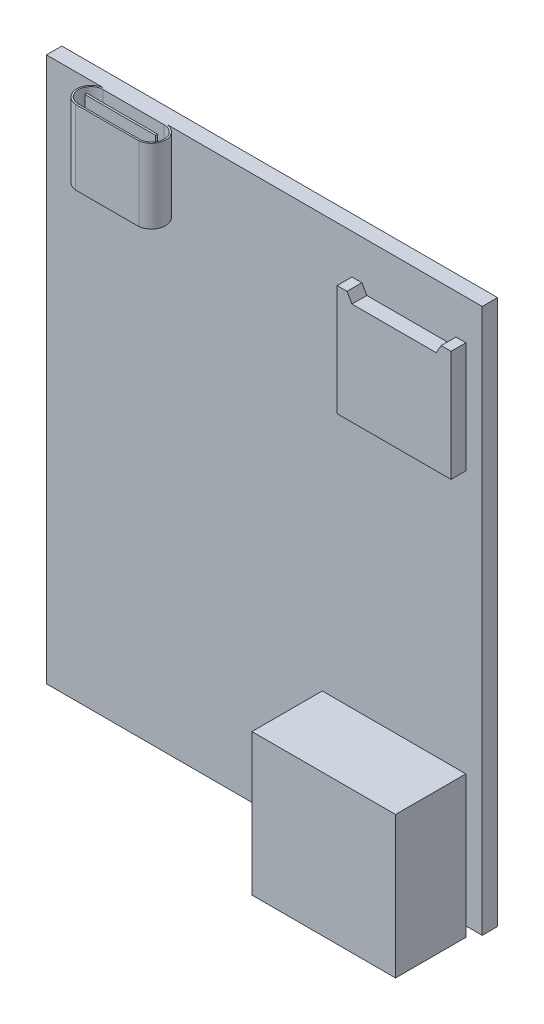
SolidWorks part; units mm, degrees
ref_plane "Front Plane" through (0, 0, 0) normal (1, 0, 0) x (0, 1, 0)
ref_plane "Top Plane" through (0, 0, 0) normal (0, 0, 1) x (0, 1, 0)
ref_plane "Right Plane" through (0, 0, 0) normal (0, 1, 0) x (-1, 0, 0)
sketch "Sketch1" plane through (0, 0, 0) normal (0, 0, 1) x (0, 1, 0)
  line L1 (-27.5, -22) -> (27.5, -22)
  line L2 (-27.5, -22) -> (-27.5, 22)
  line L3 (-27.5, 22) -> (27.5, 22)
  line L4 (27.5, -22) -> (27.5, 22)
  line L5 (-27.5, -22) -> (27.5, 22) construction
  line L6 (-27.5, 22) -> (27.5, -22) construction
  point P0 (0, 0)
  dimension "D1" = 55
  dimension "D2" = 44
extrude "Boss-Extrude1" add sketch "Sketch1" along normal blind 1.55
sketch "Sketch2" plane through (0, 0, 1.55) normal (0, 0, 1) x (1, 0, 0)
  line L0 (22, -27.5) -> (22, 27.5) construction
  line L1 (5.85, -14.2) -> (20.35, -14.2)
  line L2 (5.85, -14.2) -> (5.85, -28.5)
  line L3 (5.85, -28.5) -> (20.35, -28.5)
  line L4 (20.35, -14.2) -> (20.35, -28.5)
  line L5 (5.85, -14.2) -> (20.35, -28.5) construction
  line L6 (5.85, -28.5) -> (20.35, -14.2) construction
  line L7 (-22, -27.5) -> (22, -27.5) construction
  point P0 (13.1, -21.35)
  dimension "D1" = 1.65
  dimension "D2" = 1
  dimension "D3" = 14.3
  dimension "D4" = 14.5
extrude "Boss-Extrude2" add sketch "Sketch2" along normal blind 7.1
sketch "Sketch3" plane through (0, -28.5, 0) normal (0, -1, 0) x (1, 0, 0)
  line L0 (5.85, 8.65) -> (20.35, 8.65) construction
  line L1 (6.175, 1.85) -> (20.025, 1.85)
  line L2 (6.175, 1.85) -> (6.175, 8.35)
  line L3 (6.175, 8.35) -> (20.025, 8.35)
  line L4 (20.025, 1.85) -> (20.025, 8.35)
  line L5 (6.175, 1.85) -> (20.025, 8.35) construction
  line L6 (6.175, 8.35) -> (20.025, 1.85) construction
  line L7 (5.85, 8.65) -> (20.35, 8.65)
  line L8 (20.35, 8.65) -> (20.35, 1.55) construction
  line L9 (20.35, 8.65) -> (20.35, 1.55)
  line L10 (13.1, 8.65) -> (13.1, 2.4652) construction
  line L11 (20.35, 5.1) -> (11.2496, 5.1) construction
  line L13 (6.875, 6.85) -> (19.325, 6.85)
  line L14 (6.875, 6.85) -> (6.875, 5.3523)
  line L15 (6.875, 5.3523) -> (19.325, 5.3523)
  line L16 (19.325, 6.85) -> (19.325, 5.3523)
  point P0 (13.1, 5.1)
  point P12 (13.1, 5.1)
  dimension "D1" = 13.85
  dimension "D2" = 6.5
  dimension "D3" = 1.5
  dimension "D4" = 0.7
  dimension "D5" = 0.7
  dimension "D6" = 1.4977
extrude "Cut-Extrude1" cut sketch "Sketch3" against normal offset from surface (13.3 mm away) 1 contours L1 L4 L3 L2 L13 L16 L15 L14 region at (13.1, -28.5, 4.8385) up to face at (13.1, -14.2, 5.1)
sketch "Sketch4" plane through (0, 0, 1.55) normal (0, 0, 1) x (1, 0, 0)
  line L0 (22, 27.5) -> (-22, 27.5) construction
  line L1 (-17.5, 27.5) -> (-8.55, 27.5)
  line L2 (-17.5, 27.5) -> (-17.5, 20)
  line L3 (-17.5, 20) -> (-8.55, 20)
  line L4 (-8.55, 27.5) -> (-8.55, 20)
  line L5 (-22, 27.5) -> (-22, -27.5) construction
  dimension "D1" = 4.5
  dimension "D2" = 7.5
  dimension "D3" = 8.95
extrude "Boss-Extrude3" add sketch "Sketch4" along normal blind 2.85
sketch "Sketch5" plane through (0, 27.5, 0) normal (0, 1, 0) x (-1, 0, 0)
  line L0 (8.55, 4.4) -> (17.5, 4.4) construction
  line L1 (8.55, 4.4) -> (17.5, 4.4) construction
  line L2 (8.55, 1.55) -> (17.5, 1.55) construction
  line L4 (13.025, 4.4) -> (13.025, 1.9427) construction
  line L7 (9.8105, 1.55) -> (8.55, 1.55)
  line L8 (8.55, 1.55) -> (8.55, 4.4)
  line L9 (8.55, 4.4) -> (9.8105, 4.4)
  line L10 (8.55, 4.4) -> (9.8105, 4.4)
  line L11 (16.2395, 4.4) -> (17.5, 4.4)
  line L12 (17.5, 4.4) -> (17.5, 2.975)
  line L13 (17.5, 2.975) -> (17.5, 1.55)
  line L14 (17.5, 1.55) -> (16.2395, 1.55)
  line L15 (9.95, 2.975) -> (16.1, 2.975) construction
  line L16 (9.95, 4.2305) -> (16.1, 4.2305)
  line L17 (9.95, 1.7195) -> (16.1, 1.7195)
  line L19 (9.45, 2.875) -> (16.6, 2.875)
  line L20 (9.45, 2.875) -> (9.45, 3.075)
  line L21 (9.45, 3.075) -> (16.6, 3.075)
  line L22 (16.6, 2.875) -> (16.6, 3.075)
  line L23 (9.45, 2.875) -> (16.6, 3.075) construction
  line L24 (9.45, 3.075) -> (16.6, 2.875) construction
  arc A0 (9.8105, 1.55) -> (9.8105, 4.4) centre (9.9857, 2.975) cw
  arc A1 (16.2395, 1.55) -> (16.2395, 4.4) centre (16.0643, 2.975) ccw
  arc A2 (9.95, 4.2305) -> (9.95, 1.7195) centre (9.95, 2.975) ccw
  arc A3 (16.1, 1.7195) -> (16.1, 4.2305) centre (16.1, 2.975) ccw
  point P17 (13.025, 2.975)
  point P22 (13.025, 2.975)
  point P27 (13.025, 1.9427)
  point P28 (0, 0)
  line M7 (17.5, 1.55) -> (17.5, 4.4)
  line M8 (17.5, 4.4) -> (8.55, 4.4)
  line M9 (8.55, 4.4) -> (8.55, 1.55)
  dimension "D1" = 1.4357
  dimension "D2" = 6.15
  dimension "D3" = 1.2555
  dimension "D4" = 7.15
  dimension "D5" = 0.2
extrude "Cut-Extrude2" cut sketch "Sketch5" against normal up to surface (7.5 mm away) contours A0 M9 M8 | L7 A0 L8 | A1 L14 M7 | A1 M7 M8 region at (-17.1905, 27.5, 1.8704) region at (-17.1905, 27.5, 4.0796) region at (-8.8595, 27.5, 4.0796) region at (-8.8595, 27.5, 1.8704) up to face at (-13.025, 20, 2.975)
extrude "Cut-Extrude3" cut sketch "Sketch5<3>" against normal offset from surface (7 mm away) 0.5 contours L17 A3 L16 A2 L22 L19 L20 L21 region at (-13.025, 27.5, 4.1404) up to face at (-13.025, 20, 2.975)
sketch "Sketch5<3>" plane through (0, 27.5, 0) normal (0, 1, 0) x (-1, 0, 0) same geometry as "Sketch5"
sketch "Sketch6" plane through (0, 0, 1.55) normal (0, 0, 1) x (1, 0, 0)
  line L0 (19.35, 23.5) -> (18.85, 22.634)
  line L1 (20.35, 12.3) -> (8.85, 12.3)
  line L2 (20.35, 12.3) -> (20.35, 23.5)
  line L3 (20.35, 23.5) -> (19.35, 23.5)
  line L4 (8.85, 12.3) -> (8.85, 23.5)
  line L5 (20.35, -28.5) -> (20.35, -14.2) construction
  line L6 (20.35, -28.5) -> (20.35, -14.2) construction
  line L7 (18.85, 22.634) -> (10.35, 22.634)
  line L8 (10.35, 22.634) -> (9.85, 23.5)
  line L9 (9.85, 23.5) -> (8.85, 23.5)
  line L10 (22, 27.5) -> (-9.8105, 27.5) construction
  point P12 (18.9133, 22.7436)
  dimension "D1" = 120
  dimension "D2" = 8.5
  dimension "D4" = 1
  dimension "D5" = 11.5
  dimension "D6" = 11.2
  dimension "D7" = 4
extrude "Boss-Extrude4" add sketch "Sketch6" along normal blind 1.5
